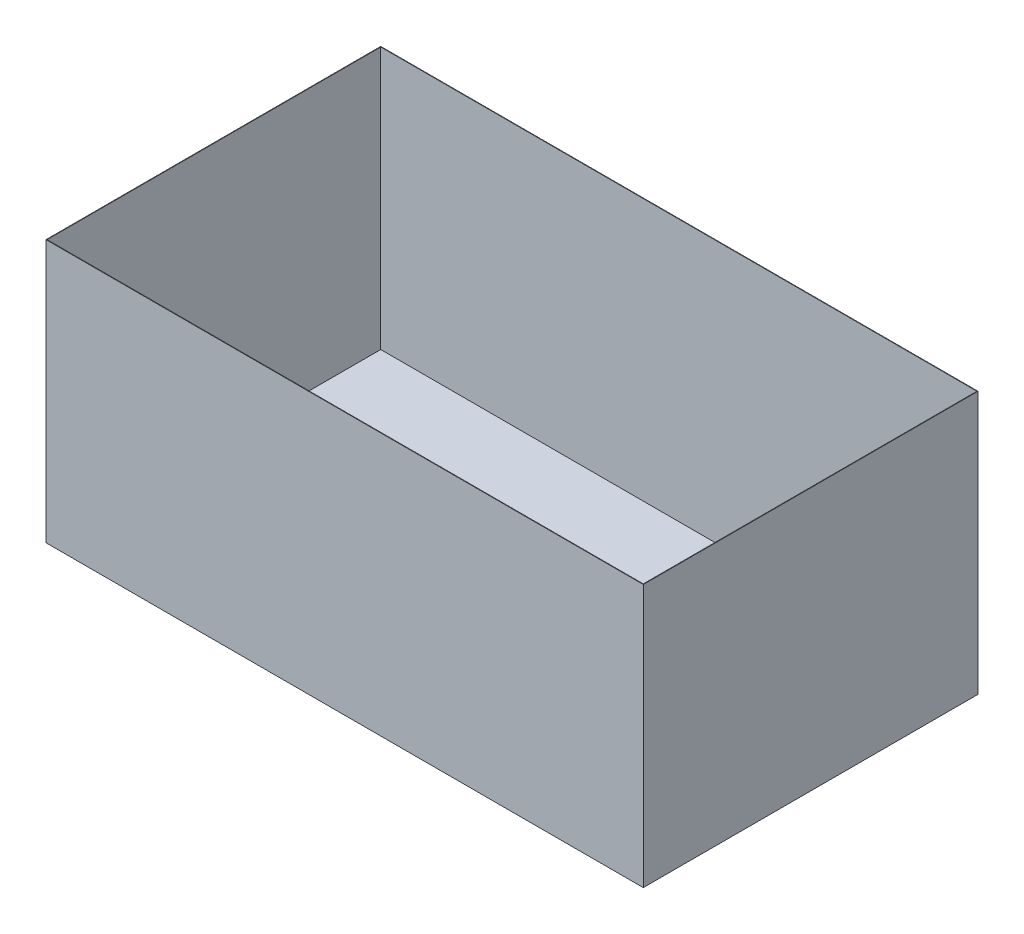
SolidWorks part; units mm, degrees
ref_plane "Front Plane" through (0, 0, 0) normal (0, 0, 1) x (1, 0, 0)
ref_plane "Top Plane" through (0, 0, 0) normal (0, 1, 0) x (1, 0, 0)
ref_plane "Right Plane" through (0, 0, 0) normal (1, 0, 0) x (0, 0, -1)
sketch "Sketch1" plane through (0, 0, 0) normal (1, 0, 0) x (0, 0, -1)
  line L1 (0, 0) -> (1295.4, 0)
  line L2 (0, 0) -> (0, 1016)
  line L3 (0, 1016) -> (1295.4, 1016)
  line L4 (1295.4, 0) -> (1295.4, 1016)
  dimension "D1" = 1295.4
  dimension "D2" = 1016
extrude "Boss-Extrude1" add sketch "Sketch1" against normal blind 2311.4
sketch "Sketch2" plane through (0, 1016, 0) normal (0, 1, 0) x (1, 0, 0)
  line L0 (-2311.4, 1295.4) -> (0, 1295.4) construction
  line L1 (-2, 2) -> (-2309.4, 2)
  line L2 (-2, 2) -> (-2, 1293.4)
  line L3 (-2, 1293.4) -> (-2309.4, 1293.4)
  line L4 (-2309.4, 2) -> (-2309.4, 1293.4)
  line L5 (-2, 2) -> (-2309.4, 1293.4) construction
  line L6 (-2, 1293.4) -> (-2309.4, 2) construction
  line L7 (0, 1295.4) -> (0, 0) construction
  line L8 (-2311.4, 0) -> (0, 0) construction
  line L9 (-2311.4, 1295.4) -> (-2311.4, 0) construction
  point P0 (-1155.7, 647.7)
  dimension "D1" = 2
  dimension "D2" = 2
  dimension "D3" = 2
  dimension "D4" = 2
extrude "Cut-Extrude1" cut sketch "Sketch2" against normal blind 1014
